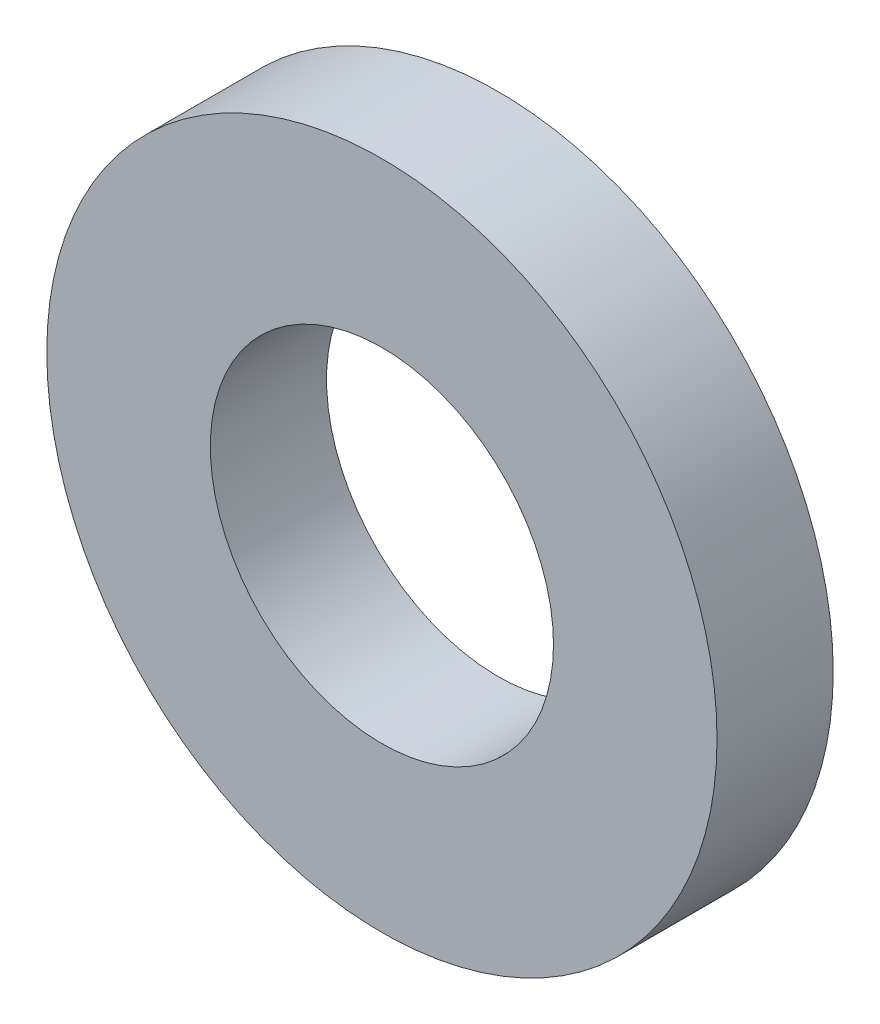
SolidWorks part; units mm, degrees
material "5052-H32"
ref_plane "Front Plane" through (0, 0, 0) normal (0, 0, 1) x (1, 0, 0)
ref_plane "Top Plane" through (0, 0, 0) normal (0, 1, 0) x (1, 0, 0)
ref_plane "Right Plane" through (0, 0, 0) normal (1, 0, 0) x (0, 0, -1)
ref_axis "Centre Axis" through (0, 0, -1.7335) along (0, 0, 1)
sketch "Sketch1" plane through (0, 0, 0) normal (0, 0, 1) x (1, 0, 0)
  circle A0 centre (0, 0) radius 2.4384
  circle A1 centre (0, 0) radius 4.7625
  dimension "ID" = 4.8768
  dimension "OD" = 9.525
extrude "Extrude1" add sketch "Sketch1" against normal blind 1.651
